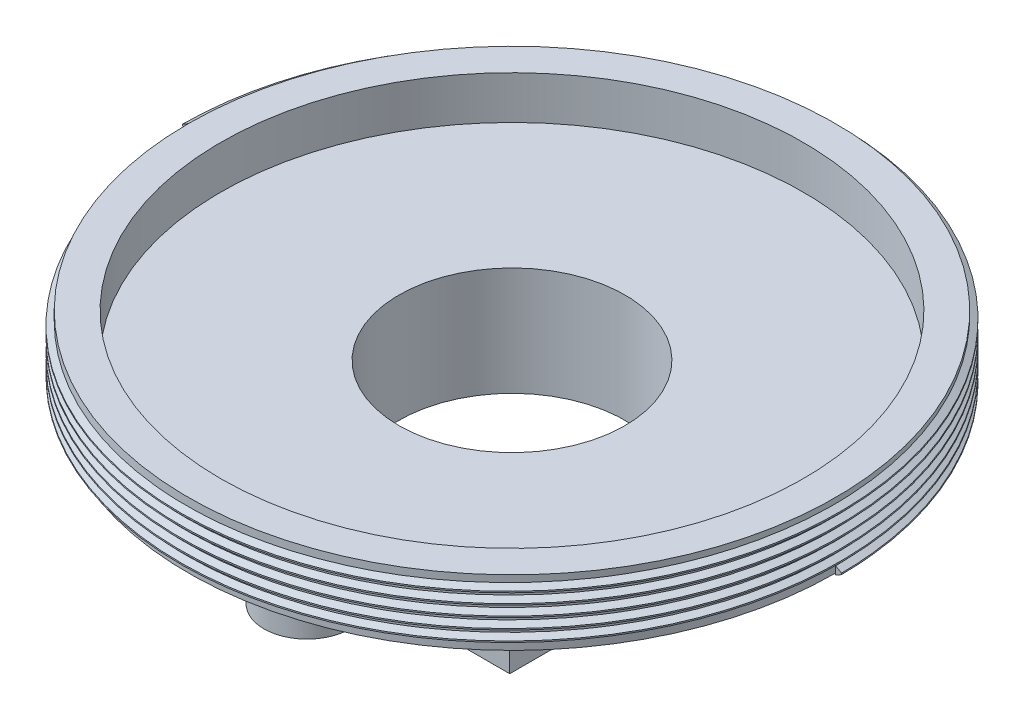
SolidWorks part; units mm, degrees
material "6061 Alloy"
ref_plane "Front Plane" through (0, 0, 0) normal (0, 0, 1) x (1, 0, 0)
ref_plane "Top Plane" through (0, 0, 0) normal (0, 1, 0) x (1, 0, 0)
ref_plane "Right Plane" through (0, 0, 0) normal (1, 0, 0) x (0, 0, -1)
sketch "Sketch1" plane through (0, 0, 0) normal (0, 1, 0) x (1, 0, 0)
  line L16 (-7.4938, 7.588) -> (-2, 7.588)
  line L33 (2, 9.488) -> (2, 7.588)
  line L34 (-2, 7.588) -> (-2, 9.488)
  line L35 (-1.9938, -7.612) -> (-7.4938, -7.612)
  line L36 (-2, -9.512) -> (-1.9938, -7.612)
  line L37 (2, -7.612) -> (2, -9.512)
  line L38 (7.5062, -7.612) -> (2, -7.612)
  line L39 (7.5062, 7.588) -> (7.5062, -7.612)
  line L40 (2, 7.588) -> (7.5062, 7.588)
  line L41 (-7.4938, -7.612) -> (-7.4938, 7.588)
  arc A4 (2, 9.488) -> (-2, 9.488) centre (0, 9.488) ccw
  arc A5 (-2, -9.512) -> (2, -9.512) centre (0, -9.512) ccw
  circle A6 centre (0, 9.488) radius 1.1
  circle A7 centre (0, -9.512) radius 1.1
  circle A8 centre (0, 0) radius 5.25
  circle A9 centre (0, 0) radius 13.519
  circle A10 centre (0, 0) radius 15.0225
  point P0 (0, 0)
  point P14 (0, 0)
  point P67 (0, 0)
  point P72 (0, 0)
  dimension "D5" = 2.2
  dimension "D11" = 10.5
  dimension "D4" = 27.038
  dimension "D6" = 30.045
  dimension "D2" = 15
  dimension "D3" = 15.2
  dimension "D8" = 2
  dimension "D10" = 1.9
  dimension "D17" = 5.5
  dimension "D18" = 4
  dimension "D19" = 19
extrude "Base" add sketch "Sketch1" against normal blind 4 contours L36 A5 L37 L38 L39 L40 L33 A4 L34 L16 L41 L35 A8 A6 A7 | A6 | A7 region at (-4.7469, 0, -7.3134) region at (0, 0, -9.488) region at (0, 0, 9.512)
extrude "Middle Holder" add sketch "Sketch1<3>" along normal blind 1.04 contours A9 A5 L36 L35 L41 L16 L34 A4 L33 L40 L39 L38 L37 | L36 A5 L37 L38 L39 L40 L33 A4 L34 L16 L41 L35 A8 A6 A7 | A7 | A6 region at (-4.7469, 0, -7.3134) region at (0, 0, -9.488) region at (0, 0, 9.512) region at (-13.1366, 0, 0)
sketch "Sketch1<3>" plane through (0, 0, 0) normal (0, 1, 0) x (1, 0, 0) same geometry as "Sketch1"
extrude "Outside Holder" add sketch "Sketch1<4>" along normal blind 3.04 contours A10 A9 region at (-14.5976, 0, 0)
sketch "Sketch1<4>" plane through (0, 0, 0) normal (0, 1, 0) x (1, 0, 0) same geometry as "Sketch1"
cosmetic thread "Cosmetic Thread1" parameters "D2"=29.045
thread "Thread1" pitch 0.5 method extrude profile "Thread Profile1" start angle 0, offset 0, length 2.75, pitch 0.5, diameter 30.045
ref_plane "Plane1" through (-15.0225, 3.04, 0) normal (0, 0, 1) x (-1, 0, 0)
sketch "Thread Profile1" plane through (-15.0225, 3.04, 0) normal (0, 0, 1) x (-1, 0, 0)
  line L0 (0, 0) -> (0, 0.5) construction
  line L1 (0, 0) -> (0.2706, 0.1562)
  line L2 (0.2706, 0.1562) -> (0.2706, 0.2187)
  line L3 (0.2706, 0.2187) -> (0, 0.375)
  line L4 (0.2706, 0.1875) -> (0, 0.1875) construction
  line L11 (0, 0) -> (0, 0.375)
  point P2 (0, 0)
  dimension "Pitch" = 0.5
  dimension "Profile_Angle" = 60
  dimension "Profile_Land" = 0.0625
  dimension "Profile_Height" = 0.2706
fillet "Fillet1" radius 1 1 edges at (-7.4938, 0, 0.012)
fillet "Fillet2" radius 1 1 edges at (7.5062, 0, 0.012)
hole_wizard "M2 Tapped Hole1" positions "Sketch5" profile "Sketch6" tap size "M2" standard "ISO"
sketch "Sketch5" plane through (0, -4, 0) normal (0, -1, 0) x (-1, 0, 0)
  point P0 (0, 9.488)
  point P3 (0, -9.512)
sketch "Sketch6" plane through (0, -4, -9.488) normal (1, 0, 0) x (0, 0, -1)
  line L0 (0, 0) -> (0, 4.4807)
  line L1 (0, 4.4807) -> (0.8, 4)
  line L2 (0.8, 4) -> (0.8, 0)
  line L5 (0.8, 0) -> (0, 0)
  line L10 (0, 4.4807) -> (-0.8, 4) construction
  line L11 (0, -6.35) -> (0, 107.95) construction
  dimension "Tap Drill Dia." = 1.6
  dimension "Tap Drill Depth" = 4
  dimension "Drill Angle" = 118
cosmetic thread "Hole Thread1" parameters "D1"=4, "D2"=2
cosmetic thread "Hole Thread2" parameters "D1"=4, "D2"=2
